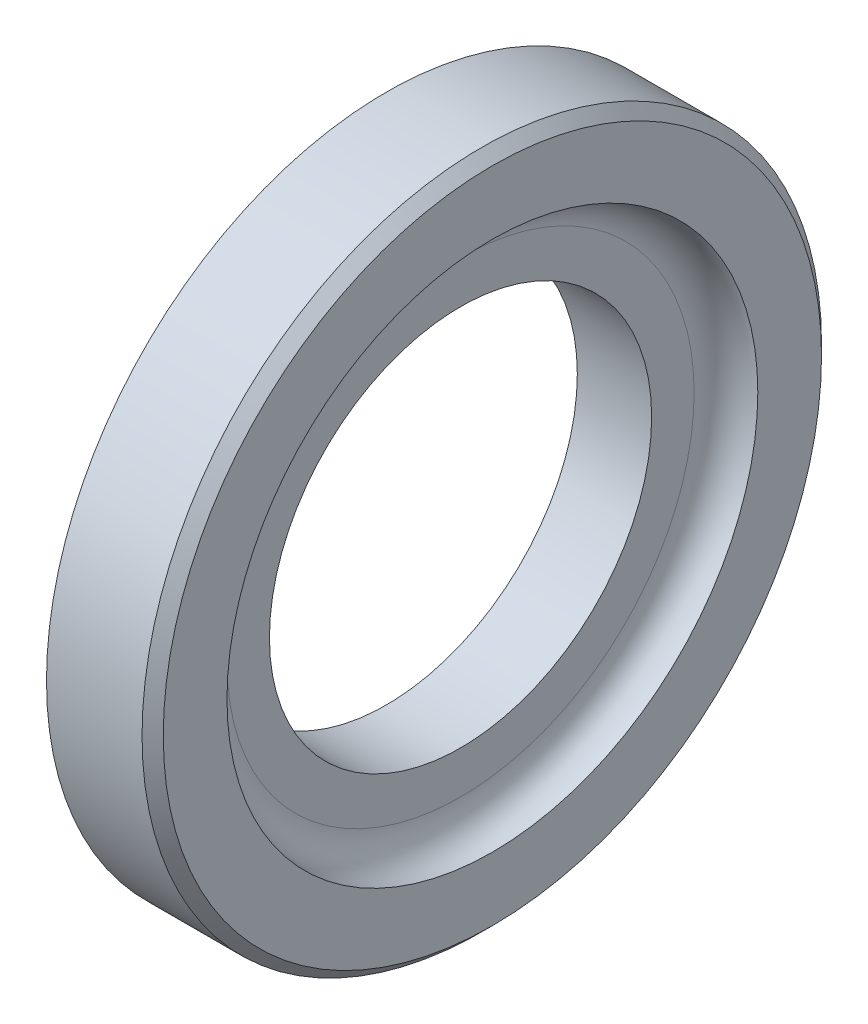
SolidWorks part; units mm, degrees
material "Plain Carbon Steel"
ref_plane "Front Plane" through (0, 0, 0) normal (0, 0, 1) x (1, 0, 0)
ref_plane "Top Plane" through (0, 0, 0) normal (0, 1, 0) x (1, 0, 0)
ref_plane "Right Plane" through (0, 0, 0) normal (1, 0, 0) x (0, 0, -1)
sketch "Sketch1" plane through (0, 0, 0) normal (0, 0, 1) x (1, 0, 0)
  line L0 (0, 0) -> (-79.3243, 0) construction
  line L2 (0, 0) -> (-10, 0)
  line L3 (0, 0) -> (0, 32)
  line L4 (0, 32) -> (-10, 32)
  line L5 (-10, 0) -> (-10, 32)
  dimension "D1" = 10
  dimension "D2" = 64
revolve "Revolve1" add sketch "Sketch1" angle 360 about L0
cosmetic thread "Cosmetic Thread1" parameters "D1"=10, "D2"=59.61
sketch "Sketch2" plane through (0, 0, 0) normal (0, 0, 1) x (1, 0, 0)
  line L0 (0, 0) -> (-34.1504, 0) construction
  line L1 (0, 0) -> (0, 25)
  line L2 (0, -32) -> (0, 32) construction
  line L3 (0, 25) -> (-3, 25)
  line L4 (-3, 25) -> (-3, 18)
  line L5 (-3, 18) -> (-10, 18)
  line L6 (-10, 32) -> (-10, -32) construction
  line L7 (-10, 18) -> (-10, 0)
  line L8 (-10, 0) -> (0, 0)
  dimension "D1" = 36
  dimension "D2" = 50
  dimension "D3" = 3
revolve "Cut-Revolve1" cut sketch "Sketch2" angle 360 about L0
fillet "Fillet1" radius 3 1 edges at (-3, 0, -25)
hole_wizard "Ø3.0mm Dowel Hole1" positions "Sketch3" profile "Sketch4" hole size "Ø3.0" standard "ISO"
sketch "Sketch3" plane through (-10, 0, 0) normal (-1, 0, 0) x (0, 0, 1)
  point P0 (0, 25)
  dimension "D1" = 25
sketch "Sketch4" plane through (-10, 25, 0) normal (0, 1, 0) x (0, 0, 1)
  line L0 (0, 0) -> (0, 3.9013)
  line L1 (0, 3.9013) -> (1.5, 3)
  line L2 (1.5, 3) -> (1.5, 0)
  line L5 (1.5, 0) -> (0, 0)
  line L10 (0, 3.9013) -> (-1.5, 3) construction
  line L11 (0, -6.35) -> (0, 107.95) construction
  dimension "Hole Dia." = 3
  dimension "Hole Depth" = 3
  dimension "Drill Angle" = 118
pattern_circular "CirPattern1" count 4 over 360 about axis through (0, 0, 0) along (1, 0, 0) of "Ø3.0mm Dowel Hole1"
chamfer "Chamfer1" distance 1 angle 45 1 edges at (0, 0, -32)
